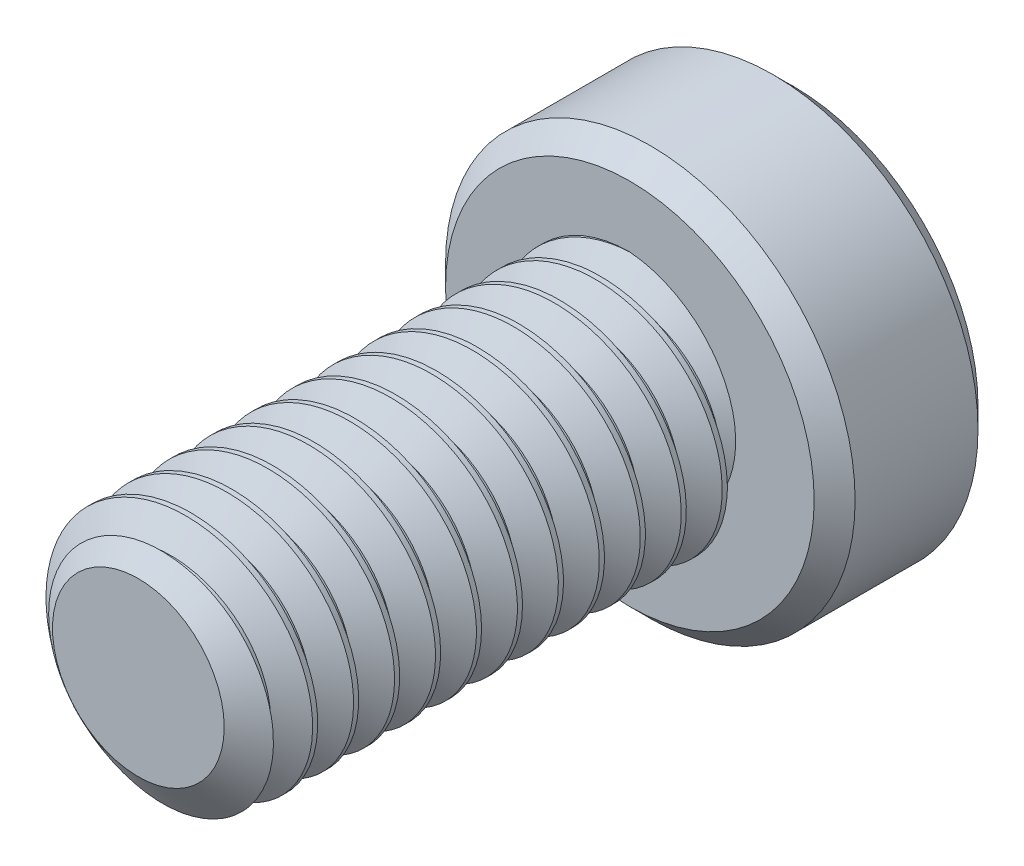
SolidWorks part; units mm, degrees
other "DetailItem1"
ref_plane "Front Plane" through (0, 0, 0) normal (0, 0, 1) x (1, 0, 0)
ref_plane "Top Plane" through (0, 0, 0) normal (0, 1, 0) x (1, 0, 0)
ref_plane "Right Plane" through (0, 0, 0) normal (1, 0, 0) x (0, 0, -1)
sketch "Sketch1" plane through (0, 0, 0) normal (0, 0, 1) x (1, 0, 0)
  circle A0 centre (0, 0) radius 3
  dimension "OD" = 6
extrude "Extrude1" add sketch "Sketch1" against normal blind 12
sketch "Sketch2" plane through (0, 0, 0) normal (0, 0, 1) x (1, 0, 0)
  circle A0 centre (0, 0) radius 3 construction
  circle A1 centre (0, 0) radius 3
curve "Helix/Spiral1" pitch 1 height 13 turns 13 parameters "pitch"=1
sketch "Sketch3" plane through (0, 0, 0) normal (1, 0, 0) x (0, 0, -1)
  line L0 (-0.875, 3) -> (-0.5, 2.3505)
  line L1 (-0.5, 2.3505) -> (-0.375, 2.3505)
  line L2 (-0.375, 2.3505) -> (0, 3)
  line L3 (-0.875, 3) -> (0, 3)
  line L4 (-0.4375, 3) -> (-0.4375, 2.3505) construction
  line L5 (-0.6875, 2.6752) -> (-0.1875, 2.6752) construction
  line L6 (0, 3) -> (0, -3) construction
  dimension "D1" = 0.125
  dimension "D2" = 0.5
  dimension "D3" = 60
sweep "Cut-Sweep1" cut profiles "Sketch3" path "Helix/Spiral1"
sketch "Sketch4" plane through (0, 0, 0) normal (1, 0, 0) x (0, 0, -1)
  line L0 (0.6327, 3) -> (0, 2.0965)
  line L1 (0, 2.0965) -> (0, 3)
  line L2 (0.6327, 3) -> (0, 3)
  line L3 (-0.875, 3) -> (0, 3) construction
  line L4 (0, 0) -> (7.0209, 0) construction
  dimension "D1" = 55
  dimension "D2" = 0.254
revolve "Cut-Revolve1" cut sketch "Sketch4" angle 360 about L4
sketch "Sketch6" plane through (0, 0, -12) normal (0, 0, -1) x (-1, 0, 0)
  circle A0 centre (0, 0) radius 5
  dimension "head dia" = 10
extrude "Extrude2" add sketch "Sketch6" along normal blind 4
sketch "Sketch7" plane through (0, 0, -16) normal (0, 0, -1) x (-1, 0, 0)
  line L1 (0, 2.3094) -> (-2, 1.1547)
  line L2 (-2, 1.1547) -> (-2, -1.1547)
  line L3 (-2, -1.1547) -> (0, -2.3094)
  line L4 (0, -2.3094) -> (2, -1.1547)
  line L5 (2, -1.1547) -> (2, 1.1547)
  line L6 (2, 1.1547) -> (0, 2.3094)
  circle A0 centre (0, 0) radius 2 construction
  dimension "hex dia" = 4
extrude "Cut-Extrude1" cut sketch "Sketch7" against normal blind 3
sketch "Sketch8" plane through (0, 0, -16) normal (0, 0, -1) x (-1, 0, 0)
  circle A0 centre (0, 0) radius 2.3094
extrude "Cut-Extrude2" cut sketch "Sketch8" against normal through all draft 45
chamfer "Chamfer1" distance 0.5 angle 45 2 edges at (-5, 0, -16) (-5, 0, -12)
sketch "Sketch10" plane through (0, 0, -12) normal (0, 0, 1) x (1, 0, 0)
  circle A1 centre (0, 0) radius 3
  circle A2 centre (0, 0) radius 3
  dimension "D1" = 0
ref_plane "Plane1" through (0, 0, -30) normal (0, 0, 1) x (1, 0, 0)
extrude "partial thread" [suppressed] add sketch "Sketch10" along normal up to surface (20 mm away) separate body
chamfer "Chamfer2" [suppressed] distance 0.12 angle 45
combine bodies "Combine1" [suppressed] operation type add bodies to combine 107 108
sketch "Sketch9" plane through (0, 0, 0) normal (1, 0, 0) x (0, 0, -1)
  line L0 (0, 3) -> (0, -3) construction
  line L1 (2.5, 3) -> (2.5, -3) construction
  dimension "D1" = 2.5
  dimension "D4" = 0.635
  dimension "D5" = 0.3302
equation "\"D3@Helix/Spiral1\" = \"screw length@Extrude1\"+\"pitch@Helix/Spiral1\""
equation "\"D1@Sketch3\" = \"pitch@Helix/Spiral1\"*.125"
equation "\"D2@Sketch3\" = \"pitch@Helix/Spiral1\"*.5"
equation "\"D1@Cut-Extrude1\" = \"hex dia@Sketch7\"*.75"
equation "\"D1@Chamfer1\" = \"head dia@Sketch6\"*.05"
equation "\"D1@Sketch9\" = \"pitch@Helix/Spiral1\"*2.5"
equation "\"D1@Chamfer2\"=\"OD@Sketch1\"*.02"
